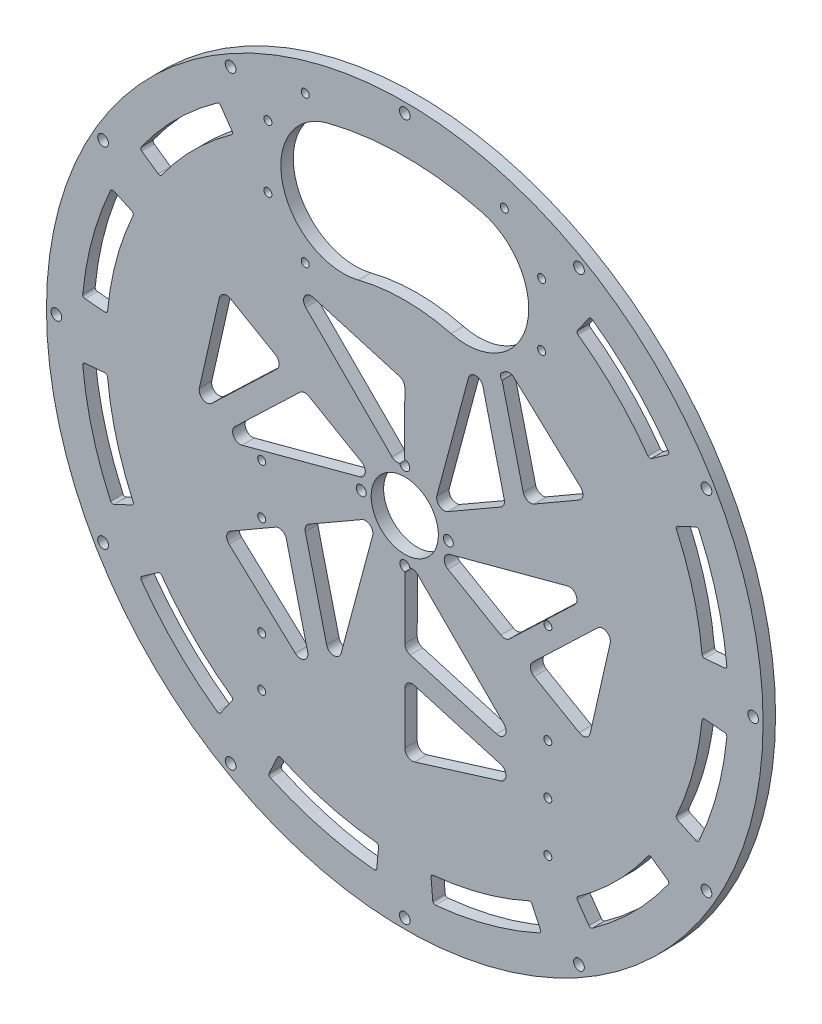
SolidWorks part; units mm, degrees
material "A-玻璃纤维"
ref_plane "前视基准面" through (0, 0, 0) normal (0, 0, 1) x (1, 0, 0)
ref_plane "上视基准面" through (0, 0, 0) normal (0, 1, 0) x (1, 0, 0)
ref_plane "右视基准面" through (0, 0, 0) normal (1, 0, 0) x (0, 0, -1)
sketch "草图1" plane through (0, 0, 0) normal (0, 0, 1) x (1, 0, 0)
  arc A1 (0, -13.5) -> (0, 13.5) centre (0, 0) ccw construction
  arc A2 (0, 144) -> (0, -144) centre (0, 0) ccw
  arc A3 (0, -144) -> (0, 144) centre (0, 0) ccw
  arc A4 (0, 144) -> (0, -144) centre (0, 0) ccw
  arc A5 (0, -144) -> (0, 144) centre (0, 0) ccw
  arc A6 (0, 13.5) -> (0, -13.5) centre (0, 0) ccw construction
  arc A7 (17.5, -2) -> (17.5, 2) centre (17.5, 0) ccw construction
  arc A8 (17.5, 2) -> (17.5, -2) centre (17.5, 0) ccw construction
  arc A9 (0, -19.5) -> (0, -15.5) centre (0, -17.5) ccw construction
  arc A10 (0, -15.5) -> (0, -19.5) centre (0, -17.5) ccw construction
  arc A11 (-15.5, 0) -> (-19.5, 0) centre (-17.5, 0) ccw construction
  arc A12 (-17.5, -2) -> (-17.5, 2) centre (-17.5, 0) ccw construction
  arc A13 (-17.5, 2) -> (-17.5, -2) centre (-17.5, 0) ccw construction
  arc A14 (0, 15.5) -> (0, 19.5) centre (0, 17.5) ccw construction
  arc A15 (0, 19.5) -> (0, 15.5) centre (0, 17.5) ccw construction
  arc A16 (0, 19.5) -> (0, 15.5) centre (0, 17.5) ccw
  arc A17 (0, 15.5) -> (0, 19.5) centre (0, 17.5) ccw
  arc A18 (-17.5, 2) -> (-17.5, -2) centre (-17.5, 0) ccw
  arc A19 (-17.5, -2) -> (-17.5, 2) centre (-17.5, 0) ccw
  arc A20 (-15.5, 0) -> (-19.5, 0) centre (-17.5, 0) ccw
  arc A21 (0, -15.5) -> (0, -19.5) centre (0, -17.5) ccw
  arc A22 (0, -19.5) -> (0, -15.5) centre (0, -17.5) ccw
  arc A23 (17.5, 2) -> (17.5, -2) centre (17.5, 0) ccw
  arc A24 (17.5, -2) -> (17.5, 2) centre (17.5, 0) ccw
  arc A25 (0, 13.5) -> (0, -13.5) centre (0, 0) ccw
  arc A26 (0, -13.5) -> (0, 13.5) centre (0, 0) ccw
  arc A27 (31.0049, 121.0938) -> (-31.0049, 121.0937) centre (0, 0) ccw construction
  arc A28 (-31.0049, 121.0937) -> (-24.8039, 71.875) centre (-24.8039, 96.875) ccw construction
  arc A29 (-24.8039, 71.875) -> (-18.6029, 72.6562) centre (-24.8039, 96.875) ccw construction
  arc A30 (24.8039, 71.875) -> (31.0049, 121.0938) centre (24.8039, 96.875) ccw construction
  arc A31 (18.6029, 72.6563) -> (24.8039, 71.875) centre (24.8039, 96.875) ccw construction
  arc A32 (18.6029, 72.6563) -> (-18.6029, 72.6562) centre (0, 0) ccw construction
  arc A33 (24.8039, 71.875) -> (31.0049, 121.0938) centre (24.8039, 96.875) ccw
  arc A34 (18.6029, 72.6563) -> (24.8039, 71.875) centre (24.8039, 96.875) ccw
  arc A35 (18.6029, 72.6563) -> (-18.6029, 72.6562) centre (0, 0) ccw
  arc A36 (-24.8039, 71.875) -> (-18.6029, 72.6562) centre (-24.8039, 96.875) ccw
  arc A37 (-31.0049, 121.0937) -> (-24.8039, 71.875) centre (-24.8039, 96.875) ccw
  arc A38 (31.0049, 121.0938) -> (-31.0049, 121.0937) centre (0, 0) ccw
  dimension "D1" = 0
extrude "凸台-拉伸1" add sketch "草图1" along normal blind 5 contours A4 A5 A38 A33 A34 A35 A36 A37 A26 A25 A24 A23 A22 A21 A19 A18 A17 A16 region at (139.9271, 0, 0)
ref_axis "基准轴1" through (-158.4, 0, 0) along (1, 0, 0)
sketch "草图2" plane through (0, 0, 5) normal (0, 0, 1) x (1, 0, 0)
  circle A0 centre (-57.5, -9.5348) radius 1.6
  circle A3 centre (-57.5, -29.5348) radius 1.6
  circle A4 centre (-57.5, -49.5348) radius 1.6
  circle A5 centre (-57.5, -69.5348) radius 1.6
  circle A6 centre (-57.5, -89.5348) radius 1.6
  circle A7 centre (57.5, -89.5348) radius 1.6
  circle A8 centre (57.5, -69.5348) radius 1.6
  circle A9 centre (57.5, -49.5348) radius 1.6
  circle A10 centre (57.5, -29.5348) radius 1.6
  circle A11 centre (57.5, -9.5348) radius 1.6
extrude "切除-拉伸1" cut sketch "草图2" against normal blind 66
sketch "草图3" plane through (0, 0, 5) normal (0, 0, 1) x (1, 0, 0)
  circle A0 centre (0, 0) radius 140 construction
  circle A1 centre (0, 140) radius 2.15
  circle A2 centre (70, 121.2436) radius 2.15
  circle A3 centre (121.2436, 70) radius 2.15
  circle A4 centre (140, 0) radius 2.15
  circle A5 centre (121.2436, -70) radius 2.15
  circle A6 centre (70, -121.2436) radius 2.15
  circle A7 centre (0, -140) radius 2.15
  circle A8 centre (-70, -121.2436) radius 2.15
  circle A9 centre (-121.2436, -70) radius 2.15
  circle A10 centre (-140, 0) radius 2.15
  circle A11 centre (-121.2436, 70) radius 2.15
  circle A12 centre (-70, 121.2436) radius 2.15
  point P29 (0, 0)
  dimension "D1" = 280
  dimension "D2" = 4.3
  dimension "D3" = 12
extrude "切除-拉伸2" cut sketch "草图3" against normal blind 10
sketch "草图4" plane through (0, 0, 5) normal (0, 0, 1) x (1, 0, 0)
  line L0 (0, 0) -> (-101.8234, 101.8234) construction
  line L1 (0, 0) -> (0, 94.1925) construction
  line L2 (-73.9891, 105.6674) -> (-69.4004, 99.114)
  line L4 (-99.114, 69.4004) -> (-105.6674, 73.9891)
  line L9 (105.6674, 73.9891) -> (99.114, 69.4004)
  line L10 (69.4004, 99.114) -> (73.9891, 105.6674)
  line L11 (128.5053, 11.2428) -> (120.5354, 10.5455)
  line L12 (109.6595, 51.1351) -> (116.9102, 54.5161)
  line L13 (116.9102, -54.5161) -> (109.6595, -51.1351)
  line L14 (120.5354, -10.5455) -> (128.5053, -11.2428)
  line L15 (73.9891, -105.6674) -> (69.4004, -99.114)
  line L16 (99.114, -69.4004) -> (105.6674, -73.9891)
  line L17 (11.2428, -128.5053) -> (10.5455, -120.5354)
  line L18 (51.1351, -109.6595) -> (54.5161, -116.9102)
  line L19 (-54.5161, -116.9102) -> (-51.1351, -109.6595)
  line L20 (-10.5455, -120.5354) -> (-11.2428, -128.5053)
  line L21 (-105.6674, -73.9891) -> (-99.114, -69.4004)
  line L22 (-69.4004, -99.114) -> (-73.9891, -105.6674)
  line L23 (-128.5053, -11.2428) -> (-120.5354, -10.5455)
  line L24 (-109.6595, -51.1351) -> (-116.9102, -54.5161)
  line L25 (-116.9102, 54.5161) -> (-109.6595, 51.1351)
  line L26 (-120.5354, 10.5455) -> (-128.5053, 11.2428)
  line L27 (-11.2428, 128.5053) -> (-10.5455, 120.5354) [skipped]
  line L28 (-51.1351, 109.6595) -> (-54.5161, 116.9102) [skipped]
  line L29 (54.5161, 116.9102) -> (51.1351, 109.6595) [skipped]
  line L30 (10.5455, 120.5354) -> (11.2428, 128.5053) [skipped]
  circle A0 centre (0, 0) radius 85 construction
  circle A1 centre (0, 0) radius 120 construction
  circle A2 centre (0, 0) radius 144 construction
  arc A3 (-69.6392, 97.7261) -> (-97.7261, 69.6392) centre (0, 0) ccw
  arc A4 (-75.3882, 105.9085) -> (-105.9085, 75.3882) centre (0, 0) ccw
  arc A5 (-105.9085, 75.3882) -> (-105.6674, 73.9891) centre (-105.0939, 74.8083) ccw
  arc A6 (-97.7261, 69.6392) -> (-99.114, 69.4004) centre (-98.5404, 70.2195) cw
  arc A7 (-69.6392, 97.7261) -> (-69.4004, 99.114) centre (-70.2195, 98.5404) ccw
  arc A8 (-75.3882, 105.9085) -> (-73.9891, 105.6674) centre (-74.8083, 105.0939) cw
  arc A21 (97.7261, 69.6392) -> (69.6392, 97.7261) centre (0, 0) ccw
  arc A22 (105.9085, 75.3882) -> (75.3882, 105.9085) centre (0, 0) ccw
  arc A23 (75.3882, 105.9085) -> (73.9891, 105.6674) centre (74.8083, 105.0939) ccw
  arc A24 (69.6392, 97.7261) -> (69.4004, 99.114) centre (70.2195, 98.5404) cw
  arc A25 (97.7261, 69.6392) -> (99.114, 69.4004) centre (98.5404, 70.2195) ccw
  arc A26 (105.9085, 75.3882) -> (105.6674, 73.9891) centre (105.0939, 74.8083) cw
  arc A27 (119.4528, 11.4463) -> (109.1723, 49.8136) centre (0, 0) ccw
  arc A28 (129.4136, 12.3338) -> (118.2424, 54.0254) centre (0, 0) ccw
  arc A29 (118.2424, 54.0254) -> (116.9102, 54.5161) centre (117.3328, 53.6098) ccw
  arc A30 (109.1723, 49.8136) -> (109.6595, 51.1351) centre (110.0821, 50.2288) cw
  arc A31 (119.4528, 11.4463) -> (120.5354, 10.5455) centre (120.4483, 11.5417) ccw
  arc A32 (129.4136, 12.3338) -> (128.5053, 11.2428) centre (128.4181, 12.2389) cw
  arc A33 (109.1723, -49.8136) -> (119.4528, -11.4463) centre (0, 0) ccw
  arc A34 (118.2424, -54.0254) -> (129.4136, -12.3338) centre (0, 0) ccw
  arc A35 (129.4136, -12.3338) -> (128.5053, -11.2428) centre (128.4181, -12.2389) ccw
  arc A36 (119.4528, -11.4463) -> (120.5354, -10.5455) centre (120.4483, -11.5417) cw
  arc A37 (109.1723, -49.8136) -> (109.6595, -51.1351) centre (110.0821, -50.2288) ccw
  arc A38 (118.2424, -54.0254) -> (116.9102, -54.5161) centre (117.3328, -53.6098) cw
  arc A39 (69.6392, -97.7261) -> (97.7261, -69.6392) centre (0, 0) ccw
  arc A40 (75.3882, -105.9085) -> (105.9085, -75.3882) centre (0, 0) ccw
  arc A41 (105.9085, -75.3882) -> (105.6674, -73.9891) centre (105.0939, -74.8083) ccw
  arc A42 (97.7261, -69.6392) -> (99.114, -69.4004) centre (98.5404, -70.2195) cw
  arc A43 (69.6392, -97.7261) -> (69.4004, -99.114) centre (70.2195, -98.5404) ccw
  arc A44 (75.3882, -105.9085) -> (73.9891, -105.6674) centre (74.8083, -105.0939) cw
  arc A45 (11.4463, -119.4528) -> (49.8136, -109.1723) centre (0, 0) ccw
  arc A46 (12.3338, -129.4136) -> (54.0254, -118.2424) centre (0, 0) ccw
  arc A47 (54.0254, -118.2424) -> (54.5161, -116.9102) centre (53.6098, -117.3328) ccw
  arc A48 (49.8136, -109.1723) -> (51.1351, -109.6595) centre (50.2288, -110.0821) cw
  arc A49 (11.4463, -119.4528) -> (10.5455, -120.5354) centre (11.5417, -120.4483) ccw
  arc A50 (12.3338, -129.4136) -> (11.2428, -128.5053) centre (12.2389, -128.4181) cw
  arc A51 (-49.8136, -109.1723) -> (-11.4463, -119.4528) centre (0, 0) ccw
  arc A52 (-54.0254, -118.2424) -> (-12.3338, -129.4136) centre (0, 0) ccw
  arc A53 (-12.3338, -129.4136) -> (-11.2428, -128.5053) centre (-12.2389, -128.4181) ccw
  arc A54 (-11.4463, -119.4528) -> (-10.5455, -120.5354) centre (-11.5417, -120.4483) cw
  arc A55 (-49.8136, -109.1723) -> (-51.1351, -109.6595) centre (-50.2288, -110.0821) ccw
  arc A56 (-54.0254, -118.2424) -> (-54.5161, -116.9102) centre (-53.6098, -117.3328) cw
  arc A57 (-97.7261, -69.6392) -> (-69.6392, -97.7261) centre (0, 0) ccw
  arc A58 (-105.9085, -75.3882) -> (-75.3882, -105.9085) centre (0, 0) ccw
  arc A59 (-75.3882, -105.9085) -> (-73.9891, -105.6674) centre (-74.8083, -105.0939) ccw
  arc A60 (-69.6392, -97.7261) -> (-69.4004, -99.114) centre (-70.2195, -98.5404) cw
  arc A61 (-97.7261, -69.6392) -> (-99.114, -69.4004) centre (-98.5404, -70.2195) ccw
  arc A62 (-105.9085, -75.3882) -> (-105.6674, -73.9891) centre (-105.0939, -74.8083) cw
  arc A63 (-119.4528, -11.4463) -> (-109.1723, -49.8136) centre (0, 0) ccw
  arc A64 (-129.4136, -12.3338) -> (-118.2424, -54.0254) centre (0, 0) ccw
  arc A65 (-118.2424, -54.0254) -> (-116.9102, -54.5161) centre (-117.3328, -53.6098) ccw
  arc A66 (-109.1723, -49.8136) -> (-109.6595, -51.1351) centre (-110.0821, -50.2288) cw
  arc A67 (-119.4528, -11.4463) -> (-120.5354, -10.5455) centre (-120.4483, -11.5417) ccw
  arc A68 (-129.4136, -12.3338) -> (-128.5053, -11.2428) centre (-128.4181, -12.2389) cw
  arc A69 (-109.1723, 49.8136) -> (-119.4528, 11.4463) centre (0, 0) ccw
  arc A70 (-118.2424, 54.0254) -> (-129.4136, 12.3338) centre (0, 0) ccw
  arc A71 (-129.4136, 12.3338) -> (-128.5053, 11.2428) centre (-128.4181, 12.2389) ccw
  arc A72 (-119.4528, 11.4463) -> (-120.5354, 10.5455) centre (-120.4483, 11.5417) cw
  arc A73 (-109.1723, 49.8136) -> (-109.6595, 51.1351) centre (-110.0821, 50.2288) ccw
  arc A74 (-118.2424, 54.0254) -> (-116.9102, 54.5161) centre (-117.3328, 53.6098) cw
  arc A75 (-11.4463, 119.4528) -> (-49.8136, 109.1723) centre (0, 0) ccw [skipped]
  arc A76 (-12.3338, 129.4136) -> (-54.0254, 118.2424) centre (0, 0) ccw [skipped]
  arc A77 (-54.0254, 118.2424) -> (-54.5161, 116.9102) centre (-53.6098, 117.3328) ccw [skipped]
  arc A78 (-49.8136, 109.1723) -> (-51.1351, 109.6595) centre (-50.2288, 110.0821) cw [skipped]
  arc A79 (-11.4463, 119.4528) -> (-10.5455, 120.5354) centre (-11.5417, 120.4483) ccw [skipped]
  arc A80 (-12.3338, 129.4136) -> (-11.2428, 128.5053) centre (-12.2389, 128.4181) cw [skipped]
  arc A81 (49.8136, 109.1723) -> (11.4463, 119.4528) centre (0, 0) ccw [skipped]
  arc A82 (54.0254, 118.2424) -> (12.3338, 129.4136) centre (0, 0) ccw [skipped]
  arc A83 (12.3338, 129.4136) -> (11.2428, 128.5053) centre (12.2389, 128.4181) ccw [skipped]
  arc A84 (11.4463, 119.4528) -> (10.5455, 120.5354) centre (11.5417, 120.4483) cw [skipped]
  arc A85 (49.8136, 109.1723) -> (51.1351, 109.6595) centre (50.2288, 110.0821) ccw [skipped]
  arc A86 (54.0254, 118.2424) -> (54.5161, 116.9102) centre (53.6098, 117.3328) cw [skipped]
  point P19 (-98.2982, 68.8292)
  point P22 (-68.8292, 98.2982)
  point P158 (0, 0)
  dimension "D1" = 240
  dimension "D2" = 170
  dimension "D4" = 130
  dimension "D6" = 1
  dimension "D3" = 45
  dimension "D5" = 10
  dimension "D7" = 12
extrude "切除-拉伸3" cut sketch "草图4" against normal blind 10
sketch "草图5" plane through (0, 0, 0) normal (0, 0, -1) x (-1, 0, 0)
  line L0 (0, 0) -> (0, 85) construction
  line L3 (0, 0) -> (60.1041, 60.1041) construction
  line L4 (2.1632, 47.4163) -> (36.85, 57.541)
  line L5 (39.8119, 52.5399) -> (5.1659, 17.8938)
  line L6 (0.0446, 20.0102) -> (0.0038, 44.5315)
  line L8 (51.4283, 25.2574) -> (77.54, 0.28)
  line L9 (82.5395, 3.111) -> (74.5121, 38.5294)
  line L10 (42.1453, 21.8348) -> (68.257, -3.1426)
  line L11 (65.4068, -8.2082) -> (18.0795, 4.4731)
  line L12 (17.3516, 9.9665) -> (38.5673, 22.2625)
  line L13 (52.002, 30.0234) -> (70.0863, 40.4643)
  line L14 (47.5877, -31.9095) -> (39.0125, -67.0115)
  line L15 (43.964, -69.9257) -> (70.6235, -45.2647)
  line L16 (39.9821, -25.5815) -> (31.407, -60.6836)
  line L17 (25.5949, -60.7481) -> (12.9136, -13.4207)
  line L18 (17.307, -10.0437) -> (38.5635, -22.269)
  line L19 (52.002, -30.0234) -> (70.0863, -40.4643)
  line L20 (-3.8406, -57.1669) -> (-38.5274, -67.2916)
  line L21 (-38.5755, -73.0368) -> (-3.8886, -83.794)
  line L22 (-2.1632, -47.4163) -> (-36.85, -57.541)
  line L23 (-39.8119, -52.5399) -> (-5.1659, -17.8938)
  line L24 (-0.0446, -20.0102) -> (-0.0038, -44.5315)
  line L25 (0, -60.0467) -> (0, -80.9287)
  line L26 (-51.4283, -25.2574) -> (-77.54, -0.28)
  line L27 (-82.5395, -3.111) -> (-74.5121, -38.5294)
  line L28 (-42.1453, -21.8348) -> (-68.257, 3.1426)
  line L29 (-65.4068, 8.2082) -> (-18.0795, -4.4731)
  line L30 (-17.3516, -9.9665) -> (-38.5673, -22.2625)
  line L31 (-52.002, -30.0234) -> (-70.0863, -40.4643)
  line L32 (-47.5877, 31.9095) -> (-39.0125, 67.0115)
  line L33 (-43.964, 69.9257) -> (-70.6235, 45.2647)
  line L34 (-39.9821, 25.5815) -> (-31.407, 60.6836)
  line L35 (-25.5949, 60.7481) -> (-12.9136, 13.4207)
  line L36 (-17.307, 10.0437) -> (-38.5635, 22.269)
  line L37 (-52.002, 30.0234) -> (-70.0863, 40.4643)
  circle A0 centre (0, 0) radius 85 construction
  arc A1 (5.1659, 17.8938) -> (0.0446, 20.0102) centre (3.0446, 20.0151) cw
  arc A2 (2.1632, 47.4163) -> (0.0038, 44.5315) centre (3.0037, 44.5365) ccw
  arc A3 (36.85, 57.541) -> (39.8119, 52.5399) centre (37.6906, 54.6612) cw
  arc A7 (18.0795, 4.4731) -> (17.3516, 9.9665) centre (18.8559, 7.3709) cw
  arc A8 (42.1453, 21.8348) -> (38.5673, 22.2625) centre (40.0716, 19.6669) ccw
  arc A9 (68.257, -3.1426) -> (65.4068, -8.2082) centre (66.1833, -5.3104) cw
  arc A10 (77.54, 0.28) -> (82.5395, 3.111) centre (79.6137, 2.4479) ccw
  arc A11 (51.4283, 25.2574) -> (52.002, 30.0234) centre (53.502, 27.4253) cw
  arc A12 (70.0863, 40.4643) -> (74.5121, 38.5294) centre (71.5863, 37.8663) cw
  arc A13 (12.9136, -13.4207) -> (17.307, -10.0437) centre (15.8113, -12.6443) cw
  arc A14 (39.9821, -25.5815) -> (38.5635, -22.269) centre (37.0678, -24.8696) ccw
  arc A15 (31.407, -60.6836) -> (25.5949, -60.7481) centre (28.4927, -59.9716) cw
  arc A16 (39.0125, -67.0115) -> (43.964, -69.9257) centre (41.9268, -67.7235) ccw
  arc A17 (47.5877, -31.9095) -> (52.002, -30.0234) centre (50.502, -32.6214) cw
  arc A18 (70.0863, -40.4643) -> (70.6235, -45.2647) centre (68.5863, -43.0624) cw
  arc A19 (-5.1659, -17.8938) -> (-0.0446, -20.0102) centre (-3.0446, -20.0151) cw
  arc A20 (-2.1632, -47.4163) -> (-0.0038, -44.5315) centre (-3.0037, -44.5365) ccw
  arc A21 (-36.85, -57.541) -> (-39.8119, -52.5399) centre (-37.6906, -54.6612) cw
  arc A22 (-38.5274, -67.2916) -> (-38.5755, -73.0368) centre (-37.6869, -70.1714) ccw
  arc A23 (-3.8406, -57.1669) -> (0, -60.0467) centre (-3, -60.0467) cw
  arc A24 (0, -80.9287) -> (-3.8886, -83.794) centre (-3, -80.9287) cw
  arc A25 (-18.0795, -4.4731) -> (-17.3516, -9.9665) centre (-18.8559, -7.3709) cw
  arc A26 (-42.1453, -21.8348) -> (-38.5673, -22.2625) centre (-40.0716, -19.6669) ccw
  arc A27 (-68.257, 3.1426) -> (-65.4068, 8.2082) centre (-66.1833, 5.3104) cw
  arc A28 (-77.54, -0.28) -> (-82.5395, -3.111) centre (-79.6137, -2.4479) ccw
  arc A29 (-51.4283, -25.2574) -> (-52.002, -30.0234) centre (-53.502, -27.4253) cw
  arc A30 (-70.0863, -40.4643) -> (-74.5121, -38.5294) centre (-71.5863, -37.8663) cw
  arc A31 (-12.9136, 13.4207) -> (-17.307, 10.0437) centre (-15.8113, 12.6443) cw
  arc A32 (-39.9821, 25.5815) -> (-38.5635, 22.269) centre (-37.0678, 24.8696) ccw
  arc A33 (-31.407, 60.6836) -> (-25.5949, 60.7481) centre (-28.4927, 59.9716) cw
  arc A34 (-39.0125, 67.0115) -> (-43.964, 69.9257) centre (-41.9268, 67.7235) ccw
  arc A35 (-47.5877, 31.9095) -> (-52.002, 30.0234) centre (-50.502, 32.6214) cw
  arc A36 (-70.0863, 40.4643) -> (-70.6235, 45.2647) centre (-68.5863, 43.0624) cw
  point P14 (0, 46.7849)
  point P19 (48.0955, 70.0844)
  point P118 (0, 0)
  dimension "D1" = 170
  dimension "D4" = 3
  dimension "D2" = 45
  dimension "D3" = 9
extrude "切除-拉伸4" cut sketch "草图5" against normal blind 10
sketch "草图6" plane through (0, 0, 0) normal (0, 0, -1) x (-1, 0, 0)
  circle A0 centre (-40, 127) radius 1.6
  circle A1 centre (-55, 110) radius 1.6
  circle A2 centre (-55, 85) radius 1.6
  circle A3 centre (-40, 68) radius 1.6
  circle A4 centre (40, 68) radius 1.6
  circle A5 centre (55, 85) radius 1.6
  circle A6 centre (55, 110) radius 1.6
  circle A7 centre (40, 127) radius 1.6
extrude "切除-拉伸5" cut sketch "草图6" against normal blind 10
